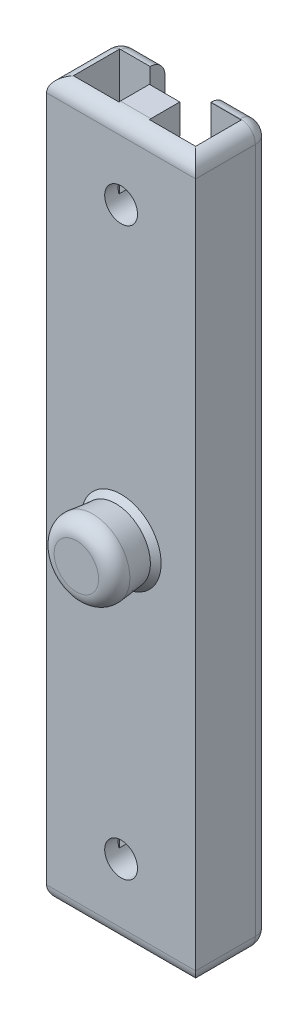
SolidWorks part; units mm, degrees
ref_plane "Front Plane" through (0, 0, 0) normal (0, 0, 1) x (1, 0, 0)
ref_plane "Top Plane" through (0, 0, 0) normal (0, 1, 0) x (1, 0, 0)
ref_plane "Right Plane" through (0, 0, 0) normal (1, 0, 0) x (0, 0, -1)
sketch "Sketch1" plane through (0, 0, 0) normal (0, 1, 0) x (1, 0, 0)
  line L1 (-12.5, -12.5) -> (12.5, -12.5)
  line L2 (-12.5, -12.5) -> (-12.5, 12.5)
  line L3 (-12.5, 12.5) -> (12.5, 12.5)
  line L4 (12.5, -12.5) -> (12.5, 12.5)
  line L5 (-12.5, -12.5) -> (12.5, 12.5) construction
  line L6 (-12.5, 12.5) -> (12.5, -12.5) construction
  point P0 (0, 0)
  dimension "D1" = 25
  dimension "D2" = 25
extrude "Boss-Extrude1" add sketch "Sketch1" along normal blind 120 contours L2 L3 L4 L1
sketch "Sketch2" plane through (0, 120, 0) normal (0, 1, 0) x (1, 0, 0)
  line L0 (0, 10.25) -> (-2.4882, 10.25) construction
  line L1 (-10.25, -10.25) -> (10.25, -10.25)
  line L2 (-10.25, -10.25) -> (-10.25, 10.25)
  line L3 (-10.25, 10.25) -> (10.25, 10.25)
  line L4 (10.25, -10.25) -> (10.25, 10.25)
  line L5 (-10.25, -10.25) -> (10.25, 10.25) construction
  line L6 (-10.25, 10.25) -> (10.25, -10.25) construction
  line L7 (-2.4882, 10.25) -> (-2.4882, 5.15)
  line L8 (-2.4882, 5.15) -> (2.6118, 5.15)
  line L9 (2.6118, 5.15) -> (2.6118, 10.25)
  line L10 (10.25, 2.4882) -> (5.15, 2.4882)
  line L11 (5.15, -2.6118) -> (10.25, -2.6118)
  line L12 (5.15, 2.4882) -> (5.15, -2.6118)
  line L13 (2.4882, -10.25) -> (2.4882, -5.15)
  line L14 (-2.6118, -5.15) -> (-2.6118, -10.25)
  line L15 (2.4882, -5.15) -> (-2.6118, -5.15)
  line L16 (-10.25, -2.4882) -> (-5.15, -2.4882)
  line L17 (-5.15, 2.6118) -> (-10.25, 2.6118)
  line L18 (-5.15, -2.4882) -> (-5.15, 2.6118)
  point P0 (0, 0)
  point P26 (0, 0)
  dimension "D1" = 20.5
  dimension "D2" = 20.5
  dimension "D3" = 5.1
  dimension "D4" = 5.1
  dimension "D5" = 7.7618
  dimension "D6" = 4
extrude "Cut-Extrude1" cut sketch "Sketch2" against normal blind 120 contours L18 L16 L2 L1 L14 L15 L13 L4 L11 L12 L10 L3 L9 L8 L7 L17 region at (0, 120, 0)
sketch "Sketch3" plane through (0, 120, 0) normal (0, 1, 0) x (1, 0, 0)
  line L0 (-12.5, 0) -> (12.5, 0)
  line L1 (-12.5, -12.5) -> (-12.5, 12.5) construction
  line L2 (12.5, -12.5) -> (12.5, 12.5) construction
  line L3 (-12.5, 0) -> (-12.5, 12.5)
  line L4 (-12.5, 12.5) -> (12.5, 12.5)
  line L5 (12.5, 12.5) -> (12.5, 0)
extrude "Cut-Extrude2" cut sketch "Sketch3" against normal blind 120
fillet "Fillet1" radius 2.5 1 edges at (-12.5, 60, 0)
fillet "Fillet2" radius 2.5 1 edges at (12.5, 60, 0)
fillet "Fillet3" radius 2.5 14 edges at (-7.575, 0, 0) (-11.7678, 0, 0.7322) (7.575, 0, 0) (11.7678, 0, 0.7322) (-7.575, 120, 0) (-11.7678, 120, 0.7322) (7.575, 120, 0) (11.7678, 120, 0.7322) (0, 0, 12.5) (-12.5, 0, 7.5) (12.5, 0, 7.5) (-12.5, 120, 7.5) (0, 120, 12.5) (12.5, 120, 7.5)
sketch "Sketch6" plane through (0, 0, 12.5) normal (0, 0, 1) x (1, 0, 0)
  line L0 (0, 117.5) -> (0, 107.5) construction
  line L1 (12.5, 117.5) -> (-12.5, 117.5) construction
  line L2 (0, 2.5) -> (0, 12.5) construction
  line L3 (-12.5, 2.5) -> (12.5, 2.5) construction
  circle A0 centre (0, 107.5) radius 2.75
  circle A1 centre (0, 12.5) radius 2.75
  dimension "D3" = 5.5
  dimension "D4" = 5.5
  dimension "D1" = 10
  dimension "D2" = 10
extrude "Cut-Extrude3" cut sketch "Sketch6" against normal blind 10
sketch "Sketch7" plane through (0, 0, 5.15) normal (0, 0, -1) x (-1, 0, 0)
  line L1 (-5.025, 99.95) -> (5.025, 99.95)
  line L2 (-5.025, 99.95) -> (-5.025, 115.05)
  line L3 (-5.025, 115.05) -> (5.025, 115.05)
  line L4 (5.025, 99.95) -> (5.025, 115.05)
  line L5 (-5.025, 99.95) -> (5.025, 115.05) construction
  line L6 (-5.025, 115.05) -> (5.025, 99.95) construction
  line L7 (-5.025, 4.95) -> (5.025, 4.95)
  line L8 (-5.025, 4.95) -> (-5.025, 20.05)
  line L9 (-5.025, 20.05) -> (5.025, 20.05)
  line L10 (5.025, 4.95) -> (5.025, 20.05)
  line L11 (-5.025, 4.95) -> (5.025, 20.05) construction
  line L12 (-5.025, 20.05) -> (5.025, 4.95) construction
  point P0 (0, 107.5)
  point P6 (0, 12.5)
  dimension "D1" = 15.1
  dimension "D2" = 10.05
  dimension "D3" = 15.1
  dimension "D4" = 10.05
extrude "Cut-Extrude4" cut sketch "Sketch7" against normal blind 2.5
sketch "Sketch8" plane through (0, 0, 12.5) normal (0, 0, 1) x (1, 0, 0)
  line L0 (0, 117.5) -> (0, 0) construction
  line L1 (12.5, 117.5) -> (-12.5, 117.5) construction
  circle A0 centre (0, 58.75) radius 5
  dimension "D1" = 10
ref_plane "Tear Drop plane" through (0, 0, 20) normal (0, 0, 1) x (1, 0, 0)
sketch "Sketch9" plane through (0, 0, 20) normal (0, 0, 1) x (1, 0, 0)
  line L1 (0, 117.5) -> (0, 2.6323) construction
  line L2 (0, 117.5) -> (0, 0) construction
  circle A0 centre (0, 58.75) radius 6.5
  dimension "D1" = 13
extrude "Boss-Extrude3" add sketch "Sketch9" against normal blind 7.5 draft 6
fillet "Fillet4" radius 2.5 1 edges at (6.5, 58.75, 20)
chamfer "Chamfer1" distance 1 angle 45 1 edges at (5.7117, 58.75, 12.5) first distance on face at (5.7117, 58.75, 12.5)
